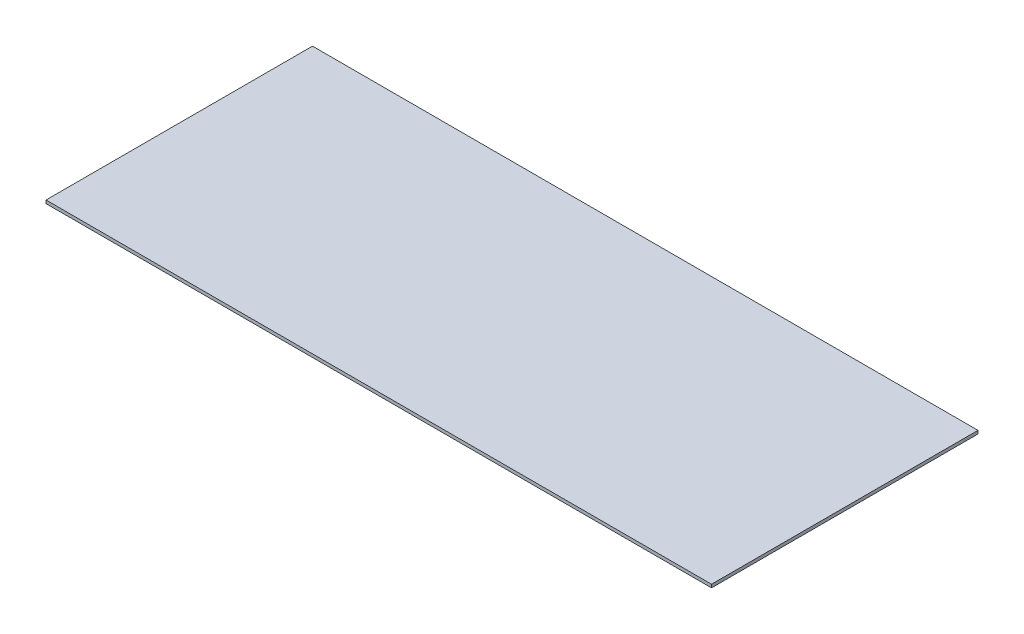
SolidWorks part; units mm, degrees
ref_plane "Front Plane" through (0, 0, 0) normal (0, 0, 1) x (1, 0, 0)
ref_plane "Top of Plywood" through (0, 0, 0) normal (0, 1, 0) x (1, 0, 0)
ref_plane "Right Plane" through (0, 0, 0) normal (1, 0, 0) x (0, 0, -1)
sketch "Interior Dim" plane through (0, 0, 0) normal (0, 1, 0) x (1, 0, 0)
  line L1 (0, 0) -> (5867.4, 0)
  line L2 (0, 0) -> (0, 2349.5)
  line L3 (0, 2349.5) -> (5867.4, 2349.5)
  line L4 (5867.4, 0) -> (5867.4, 2349.5)
  dimension "D1" = 5867.4
  dimension "D2" = 2349.5
sketch "Stud Centerlines" plane through (0, 0, 0) normal (0, 1, 0) x (1, 0, 0)
  line L0 (19.05, 19.05) -> (19.05, 2330.45) construction
  line L1 (19.05, 2330.45) -> (5867.4, 2330.45) construction
  line L2 (5867.4, 0) -> (5867.4, 2349.5) construction
  line L3 (5867.4, 19.05) -> (19.05, 19.05) construction
  line L4 (0, 0) -> (0, 2349.5) construction
  line L5 (0, 2349.5) -> (5867.4, 2349.5) construction
  line L6 (0, 0) -> (5867.4, 0) construction
  line L8 (4121.15, 2330.45) -> (4121.15, 19.05) construction
  line L9 (1771.65, 2330.45) -> (1771.65, 19.05) construction
  line L10 (19.05, 2051.05) -> (4121.15, 2051.05) construction
  dimension "D1" = 19.05
  dimension "D2" = 19.05
  dimension "D3" = 19.05
  dimension "D5" = 279.4
  dimension "D6" = 1752.6
  dimension "D7" = 2349.5
sketch "Gypsum Board" plane through (0, 0, 0) normal (0, 1, 0) x (1, 0, 0)
  line L0 (38.1, 38.1) -> (38.1, 2311.4)
  line L1 (38.1, 2311.4) -> (5867.4, 2311.4)
  line L2 (5867.4, 0) -> (5867.4, 2349.5) construction
  line L3 (50.8, 2298.7) -> (50.8, 50.8)
  line L4 (38.1, 38.1) -> (5867.4, 38.1)
  line L5 (50.8, 50.8) -> (5867.4, 50.8)
  line L6 (19.05, 19.05) -> (19.05, 2330.45) construction
  line L7 (19.05, 2330.45) -> (5867.4, 2330.45) construction
  line L8 (5867.4, 19.05) -> (19.05, 19.05) construction
  line L9 (4165.6, 50.8) -> (4165.6, 2095.5)
  line L10 (50.8, 2298.7) -> (5867.4, 2298.7)
  line L11 (4165.6, 2095.5) -> (4178.3, 2095.5)
  line L12 (4178.3, 2095.5) -> (4178.3, 50.8)
  line L13 (4121.15, 2330.45) -> (4121.15, 19.05) construction
  line L14 (19.05, 2051.05) -> (4121.15, 2051.05) construction
  line L15 (5867.4, 2311.4) -> (5867.4, 2298.7)
  line L16 (5867.4, 50.8) -> (5867.4, 38.1)
  line L17 (4165.6, 50.8) -> (4178.3, 50.8)
  dimension "D1" = 19.05
  dimension "D2" = 19.05
  dimension "D3" = 12.7
  dimension "D4" = 12.7
  dimension "D5" = 12.7
  dimension "D6" = 19.05
  dimension "D7" = 44.45
  dimension "D8" = 12.7
  dimension "D9" = 44.45
sketch "PVC" plane through (0, 0, 0) normal (0, 1, 0) x (1, 0, 0)
  line L0 (50.8, 50.8) -> (50.8, 2006.6)
  line L1 (4076.7, 50.8) -> (1841.5, 50.8)
  line L2 (50.8, 50.8) -> (1701.8, 50.8)
  line L3 (1701.8, 50.8) -> (1701.8, 2006.6)
  line L4 (1701.8, 2006.6) -> (50.8, 2006.6)
  line L5 (50.8, 2298.7) -> (50.8, 50.8) construction
  line L6 (19.05, 2051.05) -> (4121.15, 2051.05) construction
  line L7 (1771.65, 2330.45) -> (1771.65, 19.05) construction
  line L8 (50.8, 50.8) -> (5867.4, 50.8) construction
  line L9 (63.5, 1993.9) -> (1689.1, 1993.9)
  line L10 (1689.1, 1993.9) -> (1689.1, 63.5)
  line L11 (1689.1, 63.5) -> (63.5, 63.5)
  line L12 (63.5, 63.5) -> (63.5, 1993.9)
  line L13 (1841.5, 2006.6) -> (4076.7, 2006.6)
  line L14 (4076.7, 2006.6) -> (4076.7, 50.8)
  line L15 (1841.5, 50.8) -> (1841.5, 2006.6)
  line L16 (4121.15, 2330.45) -> (4121.15, 19.05) construction
  line L17 (1854.2, 1993.9) -> (1854.2, 63.5)
  line L18 (1854.2, 63.5) -> (4064, 63.5)
  line L19 (4064, 63.5) -> (4064, 1993.9)
  line L20 (4064, 1993.9) -> (1854.2, 1993.9)
  dimension "D1" = 0
  dimension "D2" = 44.45
  dimension "D3" = 69.85
  dimension "D4" = 0
  dimension "D5" = 12.7
  dimension "D6" = 12.7
  dimension "D7" = 12.7
  dimension "D8" = 12.7
  dimension "D9" = 69.85
  dimension "D10" = 44.45
  dimension "D11" = 12.7
  dimension "D12" = 12.7
  dimension "D13" = 12.7
  dimension "D14" = 12.7
sketch "Open Indoor Space" plane through (0, 0, 0) normal (0, 1, 0) x (1, 0, 0)
  line L0 (4178.3, 2095.5) -> (4165.6, 2095.5)
  line L1 (63.5, 63.5) -> (1689.1, 63.5)
  line L2 (63.5, 63.5) -> (63.5, 1993.9)
  line L3 (63.5, 1993.9) -> (1689.1, 1993.9)
  line L4 (1689.1, 63.5) -> (1689.1, 1993.9)
  line L5 (1854.2, 63.5) -> (4064, 63.5)
  line L6 (1854.2, 63.5) -> (1854.2, 1993.9)
  line L7 (1854.2, 1993.9) -> (4064, 1993.9)
  line L8 (4064, 63.5) -> (4064, 1993.9)
  line L9 (4165.6, 2095.5) -> (50.8, 2095.5)
  line L10 (50.8, 2298.7) -> (50.8, 50.8) construction
  line L11 (50.8, 2095.5) -> (50.8, 2298.7)
  line L12 (50.8, 2298.7) -> (5867.4, 2298.7)
  line L13 (5867.4, 2298.7) -> (5867.4, 50.8)
  line L14 (5867.4, 50.8) -> (4178.3, 50.8)
  line L15 (4178.3, 50.8) -> (4178.3, 2095.5)
ref_plane "Interior Roof" through (0, 2381.25, 0) normal (0, 1, 0) x (1, 0, 0)
ref_plane "Bottom of Plywood" through (0, -27.94, 0) normal (0, 1, 0) x (1, 0, 0)
sketch "Sketch4" plane through (0, 0, 0) normal (0, 1, 0) x (1, 0, 0)
  line L1 (0, 0) -> (5867.4, 0)
  line L2 (0, 0) -> (0, 2349.5)
  line L3 (0, 2349.5) -> (5867.4, 2349.5)
  line L4 (5867.4, 0) -> (5867.4, 2349.5)
extrude "Boss-Extrude2" add sketch "Sketch4" against normal up to surface (27.94 mm away) up to plane "Bottom of Plywood"
sketch "Sketch5" plane through (0, 0, 0) normal (0, 1, 0) x (1, 0, 0)
  line L0 (177.8, 63.5) -> (177.8, 0)
  line L1 (1689.1, 63.5) -> (63.5, 63.5) construction
  line L2 (0, 0) -> (5867.4, 0) construction
  line L3 (1168.4, 63.5) -> (1168.4, 0)
  line L4 (3022.6, 63.5) -> (3022.6, 0)
  line L5 (19.05, 19.05) -> (19.05, 2330.45) construction
  line L6 (1930.4, 63.5) -> (1930.4, 0)
  line L7 (1771.65, 2330.45) -> (1771.65, 19.05) construction
  dimension "D1" = 990.6
  dimension "D2" = 158.75
  dimension "D3" = 158.75
  dimension "D4" = 1092.2
ref_plane "Bottom of Roof Drywall" through (0, 2266.95, 0) normal (0, 1, 0) x (1, 0, 0)
ref_plane "Top of Insulated Subfloor" through (0, 40.64, 0) normal (0, 1, 0) x (1, 0, 0)
ref_plane "Top of Vinyl Flooring" through (0, 43.815, 0) normal (0, 1, 0) x (1, 0, 0)
sketch "Bathroom Floorspace" plane through (0, 0, 0) normal (0, 1, 0) x (1, 0, 0)
  line L1 (63.5, 1993.9) -> (1689.1, 1993.9)
  line L2 (63.5, 1993.9) -> (63.5, 63.5)
  line L3 (63.5, 63.5) -> (1689.1, 63.5)
  line L4 (1689.1, 1993.9) -> (1689.1, 63.5)
  line L5 (1854.2, 1993.9) -> (4064, 1993.9)
  line L6 (1854.2, 1993.9) -> (1854.2, 63.5)
  line L7 (1854.2, 63.5) -> (4064, 63.5)
  line L8 (4064, 1993.9) -> (4064, 63.5)
ref_plane "Top of Roof Drywall" through (0, 2279.65, 0) normal (0, 1, 0) x (1, 0, 0)
sketch "Drywall Roof Area" plane through (0, 0, 0) normal (0, 1, 0) x (1, 0, 0)
  line L0 (38.1, 38.1) -> (5867.4, 38.1) construction
  line L1 (38.1, 38.1) -> (1701.8, 38.1)
  line L2 (38.1, 38.1) -> (38.1, 2006.6)
  line L3 (38.1, 2006.6) -> (1701.8, 2006.6)
  line L4 (1701.8, 38.1) -> (1701.8, 2006.6)
  line L5 (4076.7, 2006.6) -> (1841.5, 2006.6)
  line L6 (4076.7, 2006.6) -> (4076.7, 38.1)
  line L7 (4076.7, 38.1) -> (1841.5, 38.1)
  line L8 (1841.5, 2006.6) -> (1841.5, 38.1)
  line L9 (4165.6, 2095.5) -> (50.8, 2095.5) construction
  line L10 (38.1, 2311.4) -> (1701.8, 2311.4)
  line L11 (38.1, 2311.4) -> (38.1, 2095.5)
  line L12 (38.1, 2095.5) -> (1701.8, 2095.5)
  line L13 (1701.8, 2311.4) -> (1701.8, 2095.5)
  line L14 (38.1, 2311.4) -> (5867.4, 2311.4) construction
  line L15 (4076.7, 2095.5) -> (1841.5, 2095.5)
  line L16 (4076.7, 2095.5) -> (4076.7, 2311.4)
  line L17 (4076.7, 2311.4) -> (1841.5, 2311.4)
  line L18 (1841.5, 2095.5) -> (1841.5, 2311.4)
  line L20 (4165.6, 38.1) -> (5867.4, 38.1)
  line L21 (4165.6, 38.1) -> (4165.6, 2311.4)
  line L22 (4165.6, 2311.4) -> (5867.4, 2311.4)
  line L23 (5867.4, 38.1) -> (5867.4, 2311.4)
ref_plane "Left Wall" through (0, 0, 0) normal (-1, 0, 0) x (0, 0, 1)
ref_plane "Back Wall" through (0, 0, -2349.5) normal (0, 0, -1) x (-1, 0, 0)
